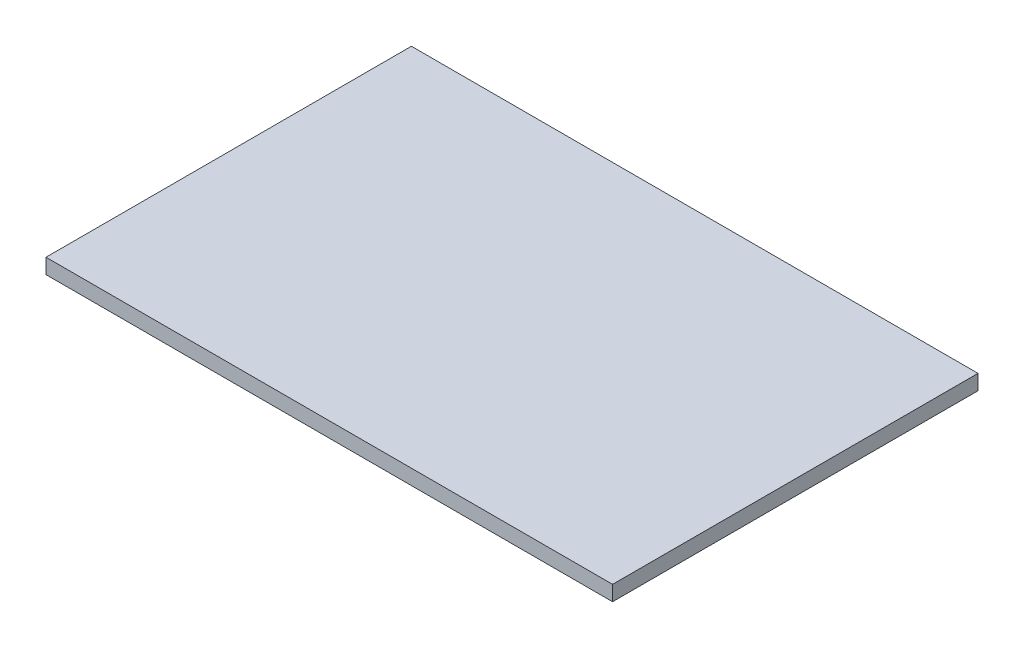
SolidWorks part; units mm, degrees
ref_plane "Front Plane" through (0, 0, 0) normal (0, 0, 1) x (1, 0, 0)
ref_plane "Top Plane" through (0, 0, 0) normal (0, 1, 0) x (1, 0, 0)
ref_plane "Right Plane" through (0, 0, 0) normal (1, 0, 0) x (0, 0, -1)
sketch "Sketch1" plane through (0, 0, 0) normal (0, 1, 0) x (1, 0, 0)
  line L1 (-169, -109) -> (169, -109)
  line L2 (-169, -109) -> (-169, 109)
  line L3 (-169, 109) -> (169, 109)
  line L4 (169, -109) -> (169, 109)
  line L5 (-169, -109) -> (169, 109) construction
  line L6 (-169, 109) -> (169, -109) construction
  point P0 (0, 0)
  dimension "D2" = 218
  dimension "D1" = 338
extrude "Boss-Extrude1" add sketch "Sketch1" along normal blind 9
equation "\"PCLength\"= 320mm'Length across I/O from PS to GPU"
equation "\"PCWidth\"= 242mm'Distance of longest part parallel to GPU(ussually GPU)"
equation "\"PCHeight\"= 172mm'Tallest point with mobo laying flat"
equation "\"WallThickness\"= 9mm'Thickness of each outer tank wall"
equation "\"ThermoBarrierThickness\"= 3mm'Thickness of barrier between hot side and cold side"
equation "\"HotSideGap\"= 25mm'Space in the hot side for a pump"
equation "\"PCClearance\"= 30mm'Clearance from top of tank to top of PC"
equation "\"RadiatorHeight\"= 275mm'Final Height from ground of radiators"
equation "\"D2@Sketch1\"=\"PCHeight\" + \"ThermoBarrierThickness\" + \"HotSideGap\" + (2 * \"WallThickness\")"
equation "\"D1@Boss-Extrude1\"=\"WallThickness\""
equation "\"D1@Sketch1\"=\"PCLength\" + (2 * \"WallThickness\")"
